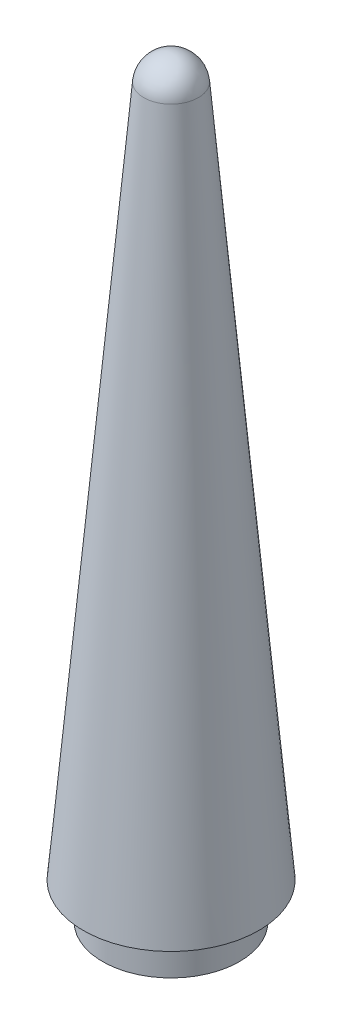
SolidWorks part; units mm, degrees
material "6061 Alloy"
ref_plane "Front Plane" through (0, 0, 0) normal (0, 0, 1) x (1, 0, 0)
ref_plane "Top Plane" through (0, 0, 0) normal (0, 1, 0) x (1, 0, 0)
ref_plane "Right Plane" through (0, 0, 0) normal (1, 0, 0) x (0, 0, -1)
sketch "Sketch2" plane through (0, 0, 0) normal (0, 0, 1) x (1, 0, 0)
  line L0 (0, 2.1015) -> (0, 141.5732)
  line L1 (0, 141.5732) -> (12.2022, 2.1015)
  line L2 (12.2022, 2.1015) -> (9.525, 2.1015)
  line L3 (9.525, 2.1015) -> (9.525, -2.9785)
  line L4 (9.525, -2.9785) -> (0, -2.9785)
  line L5 (0, -2.9785) -> (0, 2.1015)
  line L6 (0, 101.6683) -> (-2.1023, 101.6683) construction
  line L7 (0, -200166.8953) -> (0, 200141.5732) construction
  line L8 (12.2022, 2.1015) -> (-12.2022, 2.1015) construction
  line L9 (0, 141.5732) -> (26.9875, -166.8953) construction
  arc A0 (3.7955, 98.1904) -> (0, 101.6683) centre (0, 97.8583) ccw
revolve "Revolve1" add sketch "Sketch2" angle 360 about L0 region at (4.3565, 39.9734, 0)
sketch "Sketch3" plane through (0, -2.9785, 0) normal (0, -1, 0) x (1, 0, 0)
  point P0 (0, 0)
hole_wizard "1/4-20 Tapped Hole1" positions "Sketch3" profile "Sketch4" tap size "1/4-20" standard "ANSI Inch"
sketch "Sketch4" plane through (0, -2.9785, 0) normal (1, 0, 0) x (0, 0, -1)
  line L0 (0, 0) -> (0, 65.0338)
  line L1 (0, 65.0338) -> (2.5527, 63.5)
  line L2 (2.5527, 63.5) -> (2.5527, 1.2573)
  line L3 (2.5527, 1.2573) -> (3.81, 0)
  line L5 (3.81, 0) -> (0, 0)
  line L6 (-2.5527, 1.2573) -> (-3.81, 0) construction
  line L10 (0, 65.0338) -> (-2.5527, 63.5) construction
  line L11 (0, -6.35) -> (0, 107.95) construction
  dimension "Tap Drill Dia." = 5.1054
  dimension "Tap Drill Depth" = 63.5
  dimension "Near C'Sink Dia." = 7.62
  dimension "Near C'Sink Angle" = 90
  dimension "Drill Angle" = 118
cosmetic thread "Hole Thread1" parameters "D1"=50.8, "D2"=6.35
